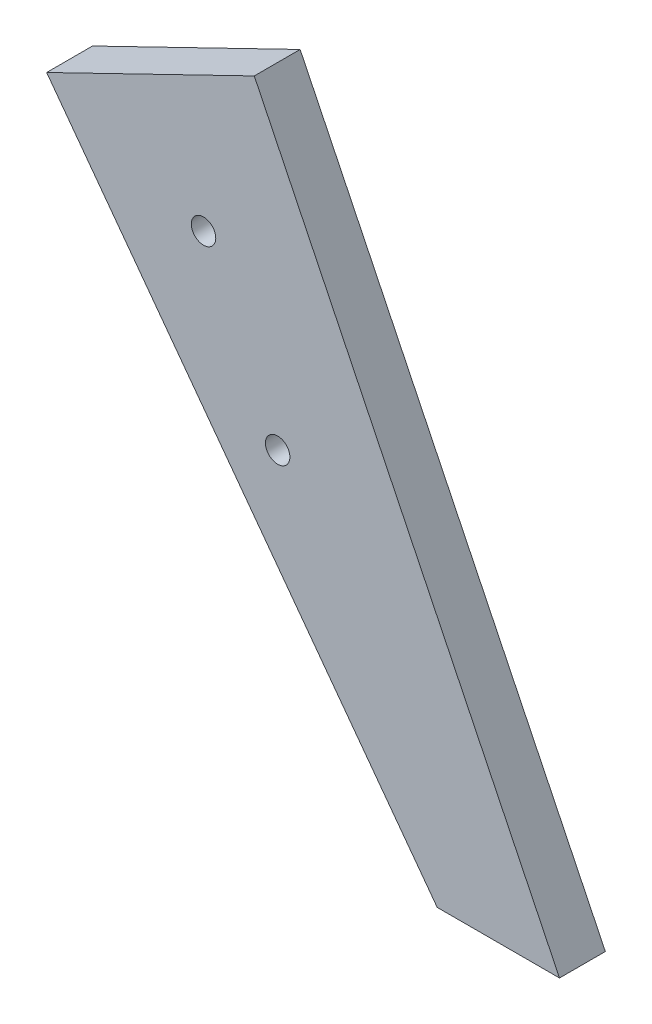
SolidWorks part; units mm, degrees
ref_plane "Front Plane" through (0, 0, 0) normal (0, 0, 1) x (1, 0, 0)
ref_plane "Top Plane" through (0, 0, 0) normal (0, 1, 0) x (1, 0, 0)
ref_plane "Right Plane" through (0, 0, 0) normal (1, 0, 0) x (0, 0, -1)
sketch "Sketch1" plane through (0, 0, 0) normal (0, 0, 1) x (1, 0, 0)
  line L0 (-20.5284, 7.7074) -> (6.6383, 20.8986)
  line L1 (6.6383, 20.8986) -> (46.5755, -61.35)
  line L2 (46.5755, -61.35) -> (30.5755, -61.35)
  line L3 (30.5755, -61.35) -> (-20.5284, 7.7074)
  circle A0 centre (0, 0) radius 1.6
  circle A1 centre (9.6969, -19.9702) radius 1.6
extrude "Boss-Extrude1" add sketch "Sketch1" along normal blind 6
ref_axis "Pivot" through (0, 0, 6.3) along (0, 0, -1)
ref_plane "LinkPin_px" through (9.6969, 0, 0) normal (1, 0, 0) x (0, 0, -1)
ref_plane "LinkPin_py" through (0, -19.9702, 0) normal (0, 1, 0) x (1, 0, 0)
ref_axis "LinkPin" through (9.6969, -19.9702, 6.3) along (0, 0, -1)
